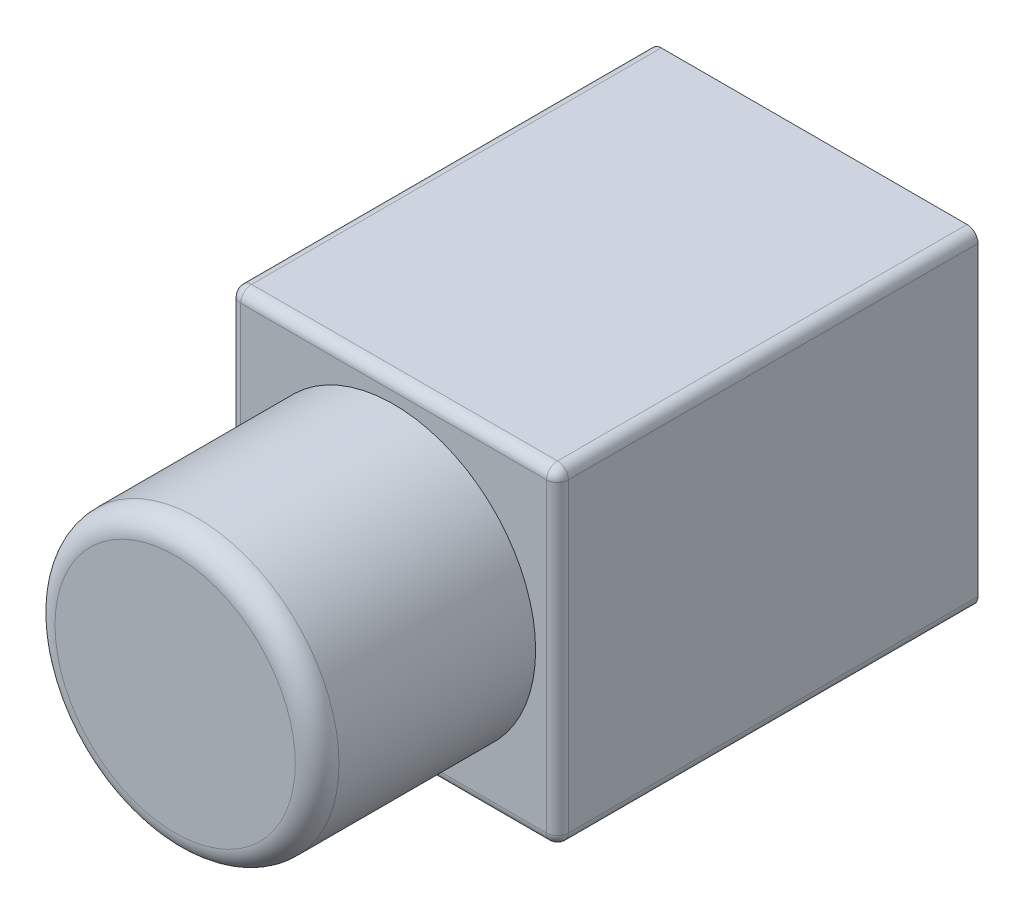
SolidWorks part; units mm, degrees
ref_plane "Front Plane" through (0, 0, 0) normal (0, 0, 1) x (1, 0, 0)
ref_plane "Top Plane" through (0, 0, 0) normal (0, 1, 0) x (1, 0, 0)
ref_plane "Right Plane" through (0, 0, 0) normal (1, 0, 0) x (0, 0, -1)
sketch "Sketch1" plane through (0, 0, 0) normal (0, 0, 1) x (1, 0, 0)
  line L0 (-11.7081, 5.6173) -> (-13.2589, 7.0647)
  line L1 (-13.2589, 7.0647) -> (16.7411, 7.0647)
  line L2 (-13.2589, 7.0647) -> (-13.2589, -22.9353)
  line L3 (-13.2589, -22.9353) -> (16.7411, -22.9353)
  line L4 (16.7411, 7.0647) -> (16.7411, -22.9353)
  line L5 (-11.7081, 5.6173) -> (15.1903, 5.6173)
  line L6 (-11.7081, 5.6173) -> (-11.7081, -21.4879)
  line L7 (-11.7081, -21.4879) -> (15.1903, -21.4879)
  line L8 (15.1903, 5.6173) -> (15.1903, -21.4879)
  line L9 (15.1903, 5.6173) -> (16.7411, 7.0647)
  line L10 (15.1903, -21.4879) -> (16.7411, -22.9353)
  line L11 (-11.7081, 5.6173) -> (15.1903, -21.4879)
  line L12 (15.1903, 1) -> (13.1903, 1)
  line L13 (13.1903, 1) -> (13.1903, 0)
  line L14 (13.1903, 0) -> (15.1903, 0)
  line L15 (15.1903, -16.9988) -> (13.1903, -16.9988)
  line L16 (13.1903, -16.9988) -> (13.1903, -15.9988)
  line L17 (13.1903, -15.9988) -> (15.1903, -15.9988)
  line L18 (10.2746, -21.4879) -> (10.2746, -19.4879)
  line L19 (10.2746, -19.4879) -> (9.2746, -19.4879)
  line L20 (9.2746, -19.4879) -> (9.2746, -21.4879)
  line L21 (-6.944, -21.4879) -> (-6.944, -19.4879)
  line L22 (-6.944, -19.4879) -> (-5.944, -19.4879)
  line L23 (-5.944, -19.4879) -> (-5.944, -21.4879)
  line L24 (-11.7081, -15.9988) -> (-9.7081, -15.9988)
  line L25 (-9.7081, -15.9988) -> (-9.7081, -16.9988)
  line L26 (-9.7081, -16.9988) -> (-11.7081, -16.9988)
  line L27 (-11.7081, 1) -> (-9.7081, 1)
  line L28 (-9.7081, 1) -> (-9.7081, 0)
  line L29 (-9.7081, 0) -> (-11.7081, 0)
  line L30 (-6.944, 3.6173) -> (-6.944, 5.6173)
  line L31 (-6.944, 3.6173) -> (-5.944, 3.6173)
  line L32 (-5.944, 3.6173) -> (-5.944, 5.6173)
  line L33 (9.2746, 5.6173) -> (9.2746, 3.6173)
  line L34 (9.2746, 3.6173) -> (10.2746, 3.6173)
  line L35 (10.2746, 3.6173) -> (10.2746, 5.6173)
  line L36 (13.1903, 1) -> (11.1903, 1)
  line L37 (11.1903, 1) -> (11.1903, 0)
  line L38 (11.1903, 0) -> (13.1903, 0)
  line L39 (13.1903, -15.9988) -> (11.1903, -15.9988)
  line L40 (11.1903, -15.9988) -> (11.1903, -16.9988)
  line L41 (-9.7081, -15.9988) -> (-7.7081, -15.9988)
  line L42 (-7.7081, -15.9988) -> (-7.7081, -16.9988)
  line L43 (-7.7081, -16.9988) -> (-9.7081, -16.9988)
  line L44 (-9.7081, 1) -> (-7.7081, 1)
  line L45 (-7.7081, 1) -> (-7.7081, 0)
  line L46 (-7.7081, 0) -> (-9.7081, 0)
  line L47 (11.1903, -16.9988) -> (13.1903, -16.9988)
  circle A0 centre (1.7411, -7.9353) radius 13
  circle A1 centre (1.7411, -7.9353) radius 9.0798
  circle A2 centre (1.7411, -7.9353) radius 11.5
  dimension "D4" = 26
  dimension "D5" = 18.1597
  dimension "D10" = 23
  dimension "D1" = 30
  dimension "D2" = 30
  dimension "D3" = 2.1213
  dimension "D6" = 2
  dimension "D7" = 1
  dimension "D8" = 2
  dimension "D9" = 2
extrude "Boss-Extrude1" add sketch "Sketch1" along normal blind 20 contours A2 L11 A0 L40 L39 L38 L37 | A2 L11 A0 L45 L46 L41 L42 | L45 A0 L46 | L38 A0 L37 | L41 A0 L42 | L40 A0 L39 region at (1.9451, 4.7492, 0) region at (-7.1105, 0.5388, 0) region at (11.4777, 0.3365, 0) region at (-7.9956, 0.3365, 0) region at (-7.9611, -16.2913, 0) region at (11.4432, -16.2913, 0)
extrude "Boss-Extrude9" add sketch "Sketch1<11>" along normal blind 1.5 contours A0 L37 L36 L12 L8 L5 L35 L34 L33 L32 L31 L30 L11 | A0 L11 L6 L27 L44 L45 | A0 L46 L29 L6 L24 L41 | A0 L42 L43 L26 L6 L7 L21 L22 L23 L20 L19 L18 L11 | A0 L11 L8 L15 L47 L40 | A0 L39 L17 L8 L14 L38 | L5 L9 L1 L0 | L8 L10 L4 L9 | L10 L7 L6 L0 L2 L3 | L29 L28 L27 L6 | A0 L45 L44 L28 L46 | L31 L32 L5 L30 | L34 L35 L5 L33 | L13 L14 L8 L12 | A0 L38 L13 L36 L37 | L17 L16 L15 L8 | A0 L40 L47 L16 L39 | L19 L20 L7 L18 | L23 L22 L21 L7 | A0 L41 L25 L43 L42 | L26 L25 L24 L6 region at (-12.1324, 3.3087, 0) region at (1.7411, 6.3542, 0) region at (-10.203, 2.5507, 0) region at (-9.3261, 5.3444, 0) region at (-6.444, 4.6173, 0) region at (-10.7081, 0.5, 0) region at (15.9788, -7.9353, 0) region at (-10.7081, -0.1633, 0) region at (-8.9063, 0.5455, 0) region at (12.3885, 0.5455, 0) region at (9.7746, 4.6173, 0) region at (-10.7081, -16.4988, 0) region at (12.6143, -0.1633, 0) region at (13.7106, -18.4977, 0) region at (12.7324, -21.2149, 0) region at (14.1903, 0.5, 0) region at (-8.8573, -16.5403, 0) region at (9.7746, -20.4879, 0) region at (14.1903, -16.4988, 0) region at (12.3394, -16.5403, 0) region at (-6.444, -20.4879, 0)
sketch "Sketch1<11>" plane through (0, 0, 0) normal (0, 0, 1) x (1, 0, 0) same geometry as "Sketch1"
extrude "Boss-Extrude10" add sketch "Sketch1<13>" against normal blind 37 contours L10 L7 L6 L0 L2 L3 | L8 L10 L4 L9 | L5 L9 L1 L0 | L34 L35 L5 L33 | L31 L32 L5 L30 | L23 L22 L21 L7 | L19 L20 L7 L18 | L17 L16 L15 L8 | L13 L14 L8 L12 | A0 L38 L13 L36 L37 | L38 A0 L37 | A0 L40 L47 L16 L39 | L40 A0 L39 | L26 L25 L24 L6 | A0 L41 L25 L43 L42 | L41 A0 L42 | A0 L45 L44 L28 L46 | L29 L28 L27 L6 | L45 A0 L46 region at (-12.1324, 3.3087, 0) region at (1.7411, 6.3542, 0) region at (-6.444, 4.6173, 0) region at (-10.7081, 0.5, 0) region at (15.9788, -7.9353, 0) region at (-8.9063, 0.5455, 0) region at (11.4777, 0.3365, 0) region at (12.3885, 0.5455, 0) region at (-7.9956, 0.3365, 0) region at (9.7746, 4.6173, 0) region at (-10.7081, -16.4988, 0) region at (14.1903, 0.5, 0) region at (-8.8573, -16.5403, 0) region at (-7.9611, -16.2913, 0) region at (9.7746, -20.4879, 0) region at (14.1903, -16.4988, 0) region at (12.3394, -16.5403, 0) region at (11.4432, -16.2913, 0) region at (-6.444, -20.4879, 0)
sketch "Sketch1<13>" plane through (0, 0, 0) normal (0, 0, 1) x (1, 0, 0) same geometry as "Sketch1"
sketch "Sketch3" plane through (0, 0, 20) normal (0, 0, 1) x (1, 0, 0)
  circle A0 centre (1.7411, -7.9353) radius 13
extrude "Boss-Extrude11" add sketch "Sketch3" along normal blind 1.5
fillet "Fillet1" radius 1 1 edges at (13.2411, -7.9353, 0)
fillet "Fillet2" radius 0.3 16 edges at (-5.944, -19.4879, -18.5) (-6.944, -19.4879, -18.5) (-7.7081, -16.9988, -18.5) (-7.7081, -15.9988, -18.4985) (-6.944, 3.6173, -18.5) (-5.944, 3.6173, -18.5) (-7.7081, 1, -18.5) (-7.7081, 0, -18.4935) (10.2746, -19.4879, -18.5) (11.1903, -16.9988, -18.5) (9.2746, -19.4879, -18.5) (11.1903, -15.9988, -18.4985) (11.1903, 1, -18.5) (11.1903, 0, -18.4935) (10.2746, 3.6173, -18.5) (9.2746, 3.6173, -18.5)
fillet "Fillet3" radius 2 1 edges at (14.7411, -7.9353, 21.5)
fillet "Fillet4" radius 1 8 edges at (-13.2589, 7.0647, -17.75) (-13.2589, -22.9353, -17.75) (16.7411, -22.9353, -17.75) (16.7411, 7.0647, -17.75) (-13.2589, -7.9353, 1.5) (1.7411, -22.9353, 1.5) (16.7411, -7.9353, 1.5) (1.7411, 7.0647, 1.5)
